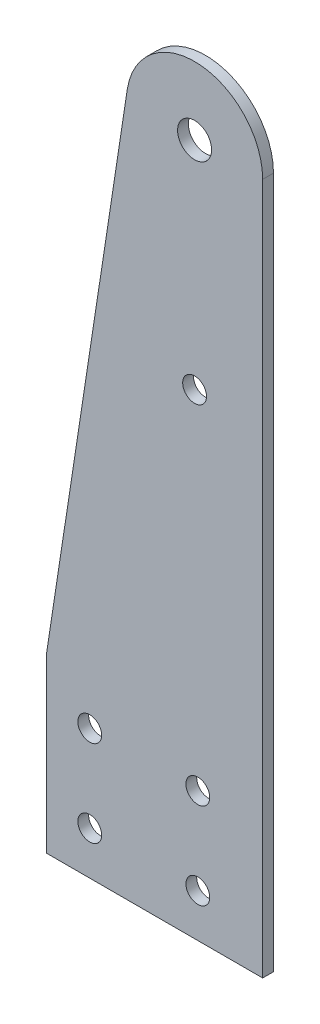
SolidWorks part; units mm, degrees
ref_plane "Front Plane" through (0, 0, 0) normal (0, 0, 1) x (1, 0, 0)
ref_plane "Top Plane" through (0, 0, 0) normal (0, 1, 0) x (1, 0, 0)
ref_plane "Right Plane" through (0, 0, 0) normal (1, 0, 0) x (0, 0, -1)
sketch "Sketch1" plane through (0, 0, 0) normal (0, 0, 1) x (1, 0, 0)
  line L0 (-31.75, -25.4) -> (31.75, -25.4)
  line L2 (31.75, -25.4) -> (31.75, 177.8)
  line L3 (-8.0209, 180.8186) -> (-31.75, 25.4)
  line L5 (-31.75, 25.4) -> (-31.75, -25.4)
  line L6 (-31.75, 25.4) -> (31.75, -25.4) construction
  line L13 (-19.05, -12.7) -> (12.7, -12.7) construction
  line L14 (-19.05, -12.7) -> (-19.05, 12.7) construction
  line L15 (-19.05, 12.7) -> (12.7, 12.7) construction
  line L16 (12.7, -12.7) -> (12.7, 12.7) construction
  line L17 (-19.05, -12.7) -> (12.7, 12.7) construction
  line L18 (-19.05, 12.7) -> (12.7, -12.7) construction
  arc A0 (-8.0209, 180.8186) -> (31.75, 177.8) centre (11.75, 177.8) cw
  circle A1 centre (11.75, 177.8) radius 5
  circle A6 centre (-19.05, 12.7) radius 3.5
  circle A7 centre (12.7, 12.7) radius 3.5
  circle A8 centre (12.7, -12.7) radius 3.5
  circle A9 centre (-19.05, -12.7) radius 3.5
  circle A10 centre (11.75, 114.3) radius 3.5
  point P7 (0, 0)
  point P8 (0, 0)
  point P9 (-3.175, 0)
  point P21 (0, 0)
  dimension "D2" = 10
  dimension "D6" = 20
  dimension "D5" = 19.05
  dimension "D9" = 7
  dimension "D1" = 50.8
  dimension "D3" = 63.5
  dimension "D4" = 152.4
  dimension "D7" = 25.4
  dimension "D8" = 31.75
  dimension "D10" = 63.5
extrude "Boss-Extrude1" add sketch "Sketch1" along normal blind 3.175
